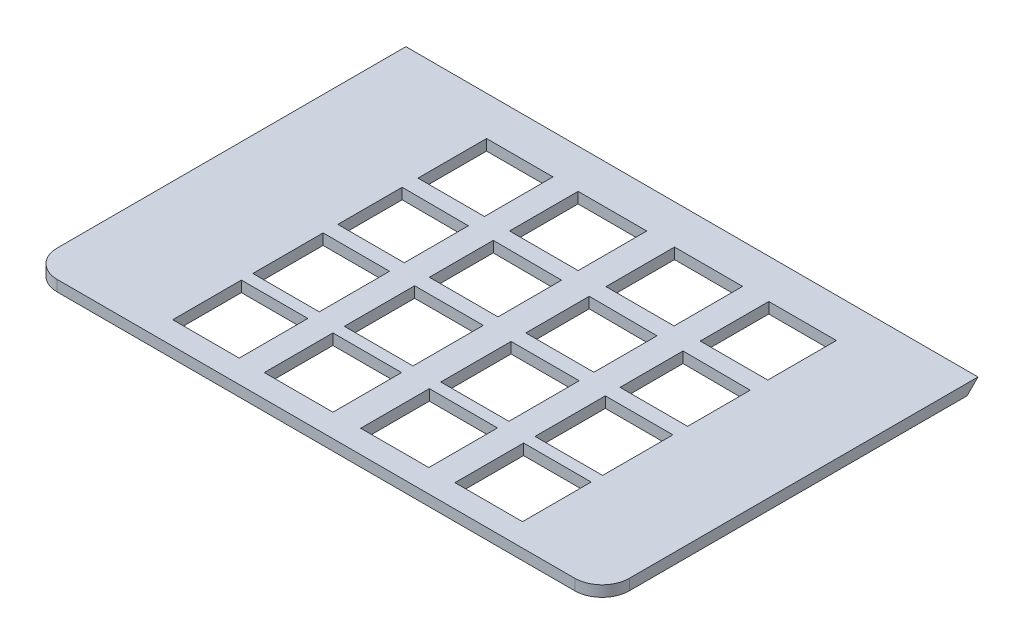
SolidWorks part; units mm, degrees
ref_plane "Front Plane" through (0, 0, 0) normal (0, 0, 1) x (1, 0, 0)
ref_plane "Top Plane" through (0, 0, 0) normal (0, 1, 0) x (1, 0, 0)
ref_plane "Right Plane" through (0, 0, 0) normal (1, 0, 0) x (0, 0, -1)
sketch "Sketch2" plane through (0, 0, 0) normal (0, 1, 0) x (1, 0, 0)
  line L0 (-29.7, -72) -> (-17.5238, -72)
  line L1 (5.3, -72) -> (17.3, -72)
  line L2 (-29.7, -72) -> (-17.5238, -72)
  line L3 (-52.5, -76) -> (52.5, -76)
  line L4 (-29.7, -72) -> (-17.5238, -72)
  line L5 (-29.7, -72) -> (-17.5238, -72)
  line L6 (-29.7, -72) -> (-17.5238, -72)
  line L7 (23.3, -72) -> (23.3, -60)
  line L8 (0, -76) -> (15, -76) construction
  line L9 (-29.7, -72) -> (-17.5238, -72)
  line L10 (52.5, -7) -> (52.5, -76)
  line L11 (23.3, -15) -> (34.3, -15)
  line L12 (17.3, -15) -> (17.3, -26)
  line L13 (5.3, -72) -> (5.3, -60)
  line L14 (5.3, -15) -> (17.3, -15)
  line L15 (-0.7, -15) -> (-0.7, -26)
  line L16 (-11.4812, -72) -> (-11.4812, -60)
  line L17 (-52.5, -76) -> (-52.5, -7)
  line L18 (-52.5, -7) -> (52.5, -7)
  line L19 (-11.4812, -15) -> (-0.7, -15)
  line L20 (-52.5, -76) -> (-29.7, -76)
  line L21 (-29.7, -76) -> (34.3, -76)
  line L22 (-29.7, -72) -> (-29.7, -60) construction
  line L23 (34.3, -72) -> (34.3, -60) construction
  line L24 (-52.5, -76) -> (-52.5, -72)
  line L25 (-52.5, -7) -> (-52.5, -76)
  line L26 (34.3, -72) -> (34.3, -60)
  line L27 (-29.7, -72) -> (-29.7, -60)
  line L28 (-29.7, -15) -> (-17.5238, -15)
  line L29 (-17.5238, -15) -> (-17.5238, -26)
  line L30 (-29.7, -15) -> (-29.7, -26)
  line L31 (-29.7, -15) -> (-29.7, -26)
  line L32 (-29.7, -26) -> (-29.7, -15)
  line L33 (-29.7, -15) -> (-29.7, -26)
  line L34 (-29.7, -41) -> (-29.7, -30)
  line L35 (-29.7, -15) -> (-29.7, -26)
  line L36 (-29.7, -41) -> (-29.7, -30)
  line L37 (-29.7, -15) -> (-29.7, -26)
  line L38 (-29.7, -56) -> (-29.7, -45)
  line L39 (-29.7, -15) -> (-29.7, -26)
  line L40 (-29.7, -60) -> (-17.5238, -60)
  line L41 (52.5, -60) -> (52.5, -56)
  line L42 (34.3, -56) -> (23.3, -56)
  line L43 (-29.7, -45) -> (-17.5238, -45)
  line L44 (52.5, -45) -> (52.5, -41)
  line L45 (34.3, -41) -> (23.3, -41)
  line L46 (-29.7, -30) -> (-17.5238, -30)
  line L47 (52.5, -30) -> (52.5, -26)
  line L48 (34.3, -26) -> (23.3, -26)
  line L49 (34.3, -26) -> (34.3, -15)
  line L50 (5.3, -72) -> (17.3, -72)
  line L51 (5.3, -72) -> (17.3, -72)
  line L52 (23.3, -72) -> (34.3, -72)
  line L53 (-11.4812, -72) -> (-0.7, -72)
  line L54 (-11.4812, -72) -> (-0.7, -72)
  line L55 (-11.4812, -72) -> (-0.7, -72)
  line L56 (-11.4812, -72) -> (-0.7, -72)
  line L57 (-11.4812, -72) -> (-0.7, -72)
  line L58 (34.3, -56) -> (34.3, -45)
  line L59 (34.3, -56) -> (34.3, -45) construction
  line L60 (23.3, -56) -> (23.3, -45)
  line L61 (17.3, -56) -> (5.3, -56)
  line L62 (23.3, -60) -> (34.3, -60)
  line L63 (17.3, -60) -> (17.3, -72)
  line L64 (5.3, -56) -> (5.3, -45)
  line L65 (-0.7, -56) -> (-11.4812, -56)
  line L66 (5.3, -60) -> (17.3, -60)
  line L67 (-0.7, -60) -> (-0.7, -72)
  line L68 (-17.5238, -56) -> (-29.7, -56)
  line L69 (-11.4812, -56) -> (-11.4812, -45)
  line L70 (-17.5238, -60) -> (-17.5238, -72)
  line L71 (-11.4812, -60) -> (-0.7, -60)
  line L72 (-17.5238, -41) -> (-29.7, -41)
  line L73 (-11.4812, -45) -> (-0.7, -45)
  line L74 (-17.5238, -45) -> (-17.5238, -56)
  line L75 (-11.4812, -41) -> (-11.4812, -30)
  line L76 (-0.7, -41) -> (-11.4812, -41)
  line L77 (5.3, -45) -> (17.3, -45)
  line L78 (-0.7, -45) -> (-0.7, -56)
  line L79 (5.3, -41) -> (5.3, -30)
  line L80 (17.3, -41) -> (5.3, -41)
  line L81 (17.3, -45) -> (17.3, -56)
  line L82 (23.3, -45) -> (34.3, -45)
  line L83 (23.3, -41) -> (23.3, -30)
  line L84 (34.3, -41) -> (34.3, -30)
  line L85 (34.3, -41) -> (34.3, -30) construction
  line L86 (34.3, -26) -> (34.3, -15) construction
  line L87 (17.3, -26) -> (5.3, -26)
  line L88 (23.3, -26) -> (23.3, -15)
  line L89 (23.3, -30) -> (34.3, -30)
  line L90 (17.3, -30) -> (17.3, -41)
  line L91 (-0.7, -26) -> (-11.4812, -26)
  line L92 (5.3, -26) -> (5.3, -15)
  line L93 (5.3, -30) -> (17.3, -30)
  line L94 (-0.7, -30) -> (-0.7, -41)
  line L95 (-17.5238, -26) -> (-29.7, -26)
  line L96 (-11.4812, -26) -> (-11.4812, -15)
  line L97 (-17.5238, -30) -> (-17.5238, -41)
  line L98 (-11.4812, -30) -> (-0.7, -30)
  line L99 (-29.7, -26) -> (-29.7, -15)
  line L100 (-29.7, -30) -> (-29.7, -41)
  line L101 (-29.7, -26) -> (-29.7, -15)
  line L102 (-29.7, -30) -> (-29.7, -41)
  line L103 (-29.7, -26) -> (-29.7, -15)
  line L104 (-29.7, -30) -> (-29.7, -41)
  line L105 (-29.7, -26) -> (-29.7, -15)
  line L106 (-29.7, -30) -> (-29.7, -41)
  line L107 (-29.7, -26) -> (-29.7, -15) construction
  line L108 (-29.7, -41) -> (-29.7, -30)
  line L109 (-29.7, -41) -> (-29.7, -30)
  line L110 (-29.7, -45) -> (-29.7, -56)
  line L111 (-29.7, -45) -> (-29.7, -56)
  line L112 (-29.7, -41) -> (-29.7, -30) construction
  line L113 (-29.7, -56) -> (-29.7, -45)
  line L114 (-29.7, -56) -> (-29.7, -45) construction
  point P0 (0, 0)
  dimension "D1" = 105
  dimension "D3" = 15
  dimension "D4" = 69
  dimension "D5" = 22.8
  dimension "D6" = 64
  dimension "D7" = 4
  dimension "D8" = 57
extrude "Boss-Extrude1" add sketch "Sketch2" along normal blind 2 contours L18 L17 L3 L10 L7 L62 L26 L52 L13 L66 L63 L1 L40 L70 L0 L27 L16 L71 L67 L53 L43 L74 L68 L38 L73 L78 L65 L69 L77 L81 L61 L64 L60 L82 region at (-51.2436, 0, 74)
fillet "Fillet1" radius 5 1 edges at (-52.5, 1, 76) type face fillet first side face at (0, 1, 76) second side face at (-52.5, 1, 41.5)
fillet "Fillet2" radius 5 1 edges at (52.5, 1, 76) type face fillet first side face at (52.5, 1, 41.5) second side face at (2.5, 1, 76)
chamfer "Chamfer1" distance 2 angle 45 1 edges at (0, 0, 7)
sketch "Sketch3" plane through (0, 2, 0) normal (0, 1, 0) x (1, 0, 0)
  line L0 (-13.7, -71.8) -> (-13.7, -59.2)
  line L1 (-13.7, -41.5) -> (-1.1, -41.5)
  line L2 (-30.5, -14.2) -> (-30.5, -26.7843)
  line L3 (23.3, -72) -> (23.3, -71.8)
  line L4 (21.3, -71.8) -> (33.7, -71.8)
  line L5 (-18.3, -71.8) -> (-18.3, -59.2)
  line L6 (21.3, -59.2) -> (33.7, -59.2)
  line L7 (21.3, -57.1) -> (33.7, -57.1)
  line L8 (21.3, -44.2) -> (33.7, -44.2)
  line L9 (21.3, -41.5) -> (33.7, -41.5)
  line L10 (21.3, -29.9388) -> (33.7, -30)
  line L11 (-1.1, -71.8) -> (-1.1, -59.2)
  line L12 (16.5, -14.2) -> (4, -14.2)
  line L13 (-1.1, -14.2) -> (-13.7, -14.2)
  line L14 (-18.3, -14.2) -> (-30.5, -14.2)
  line L15 (4, -71.8) -> (4, -59.2)
  line L16 (-13.7, -26.7843) -> (-13.7, -14.2)
  line L17 (16.5, -71.8) -> (16.5, -59.2)
  line L18 (-13.7, -29.7662) -> (-1.1, -29.8284)
  line L19 (21.3, -71.8) -> (21.3, -59.2)
  line L20 (-13.7, -44.2) -> (-1.1, -44.2)
  line L21 (33.7, -71.8) -> (33.7, -59.2)
  line L22 (-13.7, -57.1) -> (-1.1, -57.1)
  line L23 (-13.7, -59.2) -> (-1.1, -59.2)
  line L24 (-13.7, -71.8) -> (-1.1, -71.8)
  line L25 (4, -71.8) -> (16.5, -71.8)
  line L26 (4, -59.2) -> (16.5, -59.2)
  line L27 (4, -57.1) -> (16.5, -57.1)
  line L28 (4, -44.2) -> (16.5, -44.2)
  line L29 (4, -41.5) -> (16.5, -41.5)
  line L30 (-30.5, -14.2) -> (-30.5, -26.7843)
  line L31 (-30.5, -57.1) -> (-18.3, -57.1)
  line L32 (-30.5, -14.2) -> (-30.5, -26.7843)
  line L33 (-30.5, -71.8) -> (-18.3, -71.8)
  line L34 (4, -29.8535) -> (16.5, -29.9152)
  line L35 (33.7, -57.1) -> (33.7, -44.2)
  line L36 (33.7, -14.2) -> (21.3, -14.2)
  line L37 (21.3, -57.1) -> (21.3, -44.2)
  line L38 (-30.5, -14.2) -> (-18.3, -14.2)
  line L39 (21.3, -41.5) -> (21.3, -29.9388)
  line L40 (-13.7, -14.2) -> (-1.1, -14.2)
  line L41 (33.7, -41.5) -> (33.7, -30)
  line L42 (4, -14.2) -> (16.5, -14.2)
  line L43 (21.3, -26.7843) -> (21.3, -14.2)
  line L44 (21.3, -14.2) -> (33.7, -14.2)
  line L45 (-30.5, -14.2) -> (-30.5, -26.7843)
  line L46 (-30.5, -26.7843) -> (-18.3, -26.7843)
  line L47 (33.7, -26.7843) -> (33.7, -14.2)
  line L48 (-13.7, -26.7843) -> (-1.1, -26.7843)
  line L49 (16.5, -26.7843) -> (16.5, -14.2)
  line L50 (4, -26.7843) -> (16.5, -26.7843)
  line L51 (21.3, -26.7843) -> (33.7, -26.7843)
  line L52 (-30.5, -14.2) -> (-30.5, -26.7843)
  line L53 (-30.5, -29.6834) -> (-18.3, -29.7436)
  line L54 (23.3, -30) -> (34.3, -30) construction
  line L55 (-30.5, -14.2) -> (-30.5, -26.7843)
  line L56 (-30.5, -41.5) -> (-18.3, -41.5)
  line L57 (-30.5, -14.2) -> (-30.5, -26.7843)
  line L58 (-30.5, -44.2) -> (-18.3, -44.2)
  line L59 (-30.5, -59.2) -> (-18.3, -59.2)
  line L60 (4, -26.7843) -> (4, -14.2)
  line L61 (-1.1, -26.7843) -> (-1.1, -14.2)
  line L62 (-18.3, -26.7843) -> (-18.3, -14.2)
  line L63 (-30.5, -29.6834) -> (-30.5, -41.5)
  line L64 (-30.5, -29.6834) -> (-30.5, -41.5)
  line L65 (-30.5, -29.6834) -> (-30.5, -41.5)
  line L66 (-30.5, -29.6834) -> (-30.5, -41.5)
  line L67 (-30.5, -29.6834) -> (-30.5, -41.5)
  line L68 (-30.5, -44.2) -> (-30.5, -57.1)
  line L69 (-30.5, -44.2) -> (-30.5, -57.1)
  line L70 (-30.5, -44.2) -> (-30.5, -57.1)
  line L71 (-18.3, -41.5) -> (-18.3, -29.7436)
  line L72 (-30.5, -59.2) -> (-30.5, -71.8)
  line L73 (-18.3, -57.1) -> (-18.3, -44.2)
  line L74 (16.5, -57.1) -> (16.5, -44.2)
  line L75 (4, -57.1) -> (4, -44.2)
  line L76 (-1.1, -57.1) -> (-1.1, -44.2)
  line L77 (-13.7, -57.1) -> (-13.7, -44.2)
  line L78 (-13.7, -41.5) -> (-13.7, -29.7662)
  line L79 (-1.1, -41.5) -> (-1.1, -29.8284)
  line L80 (4, -41.5) -> (4, -29.8535)
  line L81 (16.5, -41.5) -> (16.5, -29.9152)
  line L82 (-18.3, -59.98) -> (-17.5238, -60)
  line L83 (-17.5238, -60) -> (-17.5238, -72)
  line L84 (-17.5238, -72) -> (-29.7, -72)
  line L85 (-29.7, -72) -> (-29.8434, -71.8)
  line L86 (-18.3, -56) -> (-17.5238, -56)
  line L87 (-17.5238, -56) -> (-29.7, -56) construction
  line L88 (-17.5238, -56) -> (-17.5238, -45)
  line L89 (-17.5238, -45) -> (-18.3, -45)
  line L90 (-18.3, -41) -> (-17.5238, -41)
  line L91 (-17.5238, -41) -> (-29.7, -41) construction
  line L92 (-17.5238, -41) -> (-17.5238, -30)
  line L93 (-17.5238, -30) -> (-18.3, -30)
  line L94 (-29.7, -30) -> (-17.5238, -30) construction
  line L95 (-18.3, -26) -> (-17.5238, -26)
  line L96 (-17.5238, -26) -> (-29.7, -26) construction
  line L97 (-17.5238, -26) -> (-17.5238, -15)
  line L98 (-17.5238, -15) -> (-18.3, -15)
  line L99 (-29.7, -15) -> (-17.5238, -15) construction
  line L100 (-1.1, -26) -> (-0.7, -26)
  line L101 (-0.7, -26) -> (-11.4812, -26) construction
  line L102 (-0.7, -26) -> (-0.7, -15)
  line L103 (-0.7, -15) -> (-1.1, -15)
  line L104 (-11.4812, -15) -> (-0.7, -15) construction
  line L105 (-1.1, -41) -> (-0.7, -41)
  line L106 (-0.7, -41) -> (-11.4812, -41) construction
  line L107 (-0.7, -41) -> (-0.7, -30)
  line L108 (-0.7, -30) -> (-1.1, -30)
  line L109 (-11.4812, -30) -> (-0.7, -30) construction
  line L110 (-1.1, -56) -> (-0.7, -56)
  line L111 (-0.7, -56) -> (-11.4812, -56) construction
  line L112 (-0.7, -56) -> (-0.7, -45)
  line L113 (-0.7, -45) -> (-1.1, -45)
  line L114 (-11.4812, -71.8) -> (-11.4812, -72)
  line L115 (-11.4812, -72) -> (-11.4812, -60) construction
  line L116 (-11.4812, -72) -> (-0.7, -72)
  line L117 (-0.7, -72) -> (-0.7, -60)
  line L118 (-0.7, -60) -> (-1.1, -60)
  line L119 (-11.4812, -60) -> (-0.7, -60) construction
  line L120 (5.2565, -71.8) -> (5.3, -72)
  line L121 (5.3, -72) -> (17.3, -72)
  line L122 (17.3, -72) -> (17.3, -60)
  line L123 (17.3, -60) -> (16.5, -60)
  line L124 (5.3, -60) -> (17.3, -60) construction
  line L125 (16.5, -56) -> (17.3, -56)
  line L126 (17.3, -56) -> (5.3, -56) construction
  line L127 (17.3, -56) -> (17.3, -45)
  line L128 (17.3, -45) -> (16.5, -45)
  line L129 (5.3, -45) -> (17.3, -45) construction
  line L130 (16.5, -41) -> (17.3, -41)
  line L131 (17.3, -41) -> (5.3, -41) construction
  line L132 (17.3, -41) -> (17.3, -30)
  line L133 (17.3, -30) -> (16.5, -30)
  line L134 (5.3, -30) -> (17.3, -30) construction
  line L135 (16.5, -26) -> (17.3, -26)
  line L136 (17.3, -26) -> (5.3, -26) construction
  line L137 (17.3, -26) -> (17.3, -15)
  line L138 (17.3, -15) -> (16.5, -15)
  line L139 (5.3, -15) -> (17.3, -15) construction
  line L140 (33.7, -15) -> (34.3, -15)
  line L141 (34.3, -15) -> (34.3, -26)
  line L142 (34.3, -26) -> (33.7, -26)
  line L143 (34.3, -26) -> (23.3, -26) construction
  line L144 (33.7, -30) -> (34.3, -30)
  line L145 (34.3, -30) -> (34.3, -41)
  line L146 (34.3, -41) -> (33.7, -41)
  line L147 (34.3, -41) -> (23.3, -41) construction
  line L148 (33.7, -45) -> (34.3, -45)
  line L149 (34.3, -45) -> (34.3, -56)
  line L150 (34.3, -56) -> (33.7, -56)
  line L151 (33.7, -60) -> (34.3, -60)
  line L152 (34.3, -60) -> (34.3, -72)
  line L153 (34.3, -72) -> (23.3, -72)
  line L154 (33.7, -60) -> (33.7, -71.8)
  line L155 (23.3, -71.8) -> (23.3, -72)
extrude "Cut-Extrude1" cut sketch "Sketch3" against normal blind 10 contours L43 L51 L47 L36 | L60 L50 L49 L12 | L48 L61 L13 L16 | L46 L62 L14 L2 | L56 L71 L53 L63 | L1 L79 L18 L78 | L29 L81 L34 L80 | L9 L41 L10 L39 | L37 L7 L35 L8 | L75 L27 L74 L28 | L77 L22 L76 L20 | L31 L73 L58 L68 | L59 L72 L33 L5 | L0 L24 L11 L23 | L26 L15 L25 L17 | L4 L21 L6 L19 region at (-7.4, 2, 65.5) region at (-7.4056, 2, 35.6486) region at (-24.4, 2, 20.4921) region at (27.5, 2, 65.5) region at (-24.4, 2, 65.5) region at (27.5, 2, 50.65) region at (27.4945, 2, 35.7347) region at (10.25, 2, 20.4921) region at (-7.4, 2, 20.4921) region at (10.25, 2, 65.5) region at (-7.4, 2, 50.65) region at (10.25, 2, 50.65) region at (10.2445, 2, 35.6922) region at (-24.4, 2, 50.65) region at (27.5, 2, 20.4921) region at (-24.4052, 2, 35.6067)
sketch "Sketch4" plane through (0, 2, 0) normal (0, 1, 0) x (1, 0, 0)
  line L0 (33.7, -15) -> (33.7, -26)
  line L1 (33.7, -26) -> (34.3, -26)
  line L2 (34.3, -26) -> (34.3, -15)
  line L3 (34.3, -15) -> (33.7, -15)
extrude "Boss-Extrude2" add sketch "Sketch4" against normal blind 2
sketch "Sketch5" plane through (0, 2, 0) normal (0, 1, 0) x (1, 0, 0)
  line L0 (33.7, -41) -> (33.7, -30)
  line L1 (33.7, -30) -> (34.3, -30)
  line L2 (34.3, -30) -> (34.3, -41)
  line L3 (34.3, -41) -> (33.7, -41)
  line L4 (33.7, -45) -> (34.3, -45)
  line L5 (34.3, -45) -> (34.3, -56)
  line L6 (34.3, -56) -> (33.7, -56)
  line L7 (33.7, -56) -> (33.7, -45)
  line L8 (33.7, -45) -> (33.7849, -45.1605)
  line L9 (33.7, -60) -> (34.3, -60)
  line L10 (34.3, -60) -> (34.3, -72)
  line L11 (34.3, -72) -> (23.3, -72)
  line L12 (23.3, -72) -> (23.3, -71.8)
  line L13 (23.3, -71.8) -> (33.7, -71.8)
  line L14 (33.7, -71.8) -> (33.7, -60)
extrude "Boss-Extrude3" add sketch "Sketch5" against normal blind 2 contours L0 L1 L2 L3 | L4 L5 L6 L7 | L10 L11 L12 L13 L14 L9
sketch "Sketch6" plane through (0, 2, 0) normal (0, 1, 0) x (1, 0, 0)
  line L0 (16.5, -15) -> (17.3, -15)
  line L1 (17.3, -15) -> (17.3, -26)
  line L2 (17.3, -26) -> (16.5, -26)
  line L3 (16.5, -26) -> (16.5, -15)
  line L4 (16.5, -30) -> (17.3, -30)
  line L5 (17.3, -30) -> (17.3, -41)
  line L6 (17.3, -41) -> (16.5, -41)
  line L7 (16.5, -41) -> (16.5, -30)
  line L8 (16.5, -45) -> (17.3, -45)
  line L9 (17.3, -45) -> (17.3, -56)
  line L10 (17.3, -56) -> (16.5, -56)
  line L11 (16.5, -56) -> (16.5, -45)
  line L12 (16.5, -60) -> (17.3, -60)
  line L13 (17.3, -60) -> (17.3, -72)
  line L14 (17.3, -72) -> (5.3, -72)
  line L15 (5.3, -72) -> (5.3, -71.8)
  line L16 (5.3, -71.8) -> (16.5, -71.8)
  line L17 (16.5, -71.8) -> (16.5, -60)
  line L18 (-1.1, -60) -> (-0.7, -60)
  line L19 (-0.7, -60) -> (-0.7, -72)
  line L20 (-0.7, -72) -> (-11.4812, -72)
  line L21 (-11.4812, -72) -> (-11.4812, -71.8)
  line L22 (-11.4812, -71.8) -> (-1.1, -71.8)
  line L23 (-1.1, -71.8) -> (-1.1, -60)
  line L24 (-18.3, -60) -> (-17.5238, -60)
  line L25 (-17.5238, -60) -> (-17.5238, -72)
  line L26 (-17.5238, -72) -> (-29.7, -72)
  line L27 (-29.7, -72) -> (-29.7, -71.8)
  line L28 (-29.7, -71.8) -> (-18.3, -71.8)
  line L29 (-18.3, -71.8) -> (-18.3, -60)
  line L30 (-1.1, -56) -> (-1.1, -45)
  line L31 (-1.1, -45) -> (-0.7, -45)
  line L32 (-0.7, -45) -> (-0.7, -56)
  line L33 (-0.7, -56) -> (-1.1, -56)
  line L35 (-1.1, -41) -> (-0.7, -41)
  line L36 (-0.7, -41) -> (-0.7, -30)
  line L37 (-0.7, -30) -> (-1.1, -30)
  line L38 (-1.1, -30) -> (-1.1, -41)
  line L39 (-1.1, -15) -> (-0.7, -15)
  line L40 (-0.7, -15) -> (-0.7, -26)
  line L41 (-0.7, -26) -> (-1.1, -26)
  line L42 (-1.1, -26) -> (-1.1, -15)
  line L43 (-18.3, -15) -> (-17.5238, -15)
  line L44 (-17.5238, -15) -> (-17.5238, -26)
  line L45 (-17.5238, -26) -> (-18.3, -26)
  line L46 (-18.3, -26) -> (-18.3, -15)
  line L47 (-18.3, -41) -> (-17.5238, -41)
  line L48 (-17.5238, -41) -> (-17.5238, -30)
  line L49 (-17.5238, -30) -> (-18.3, -30)
  line L50 (-18.3, -30) -> (-18.3, -41)
  line L51 (-18.3, -45) -> (-17.5238, -45)
  line L52 (-17.5238, -45) -> (-17.5238, -56)
  line L53 (-17.5238, -56) -> (-18.3, -56)
  line L54 (-18.3, -56) -> (-18.3, -45)
extrude "Boss-Extrude4" add sketch "Sketch6" against normal blind 2
